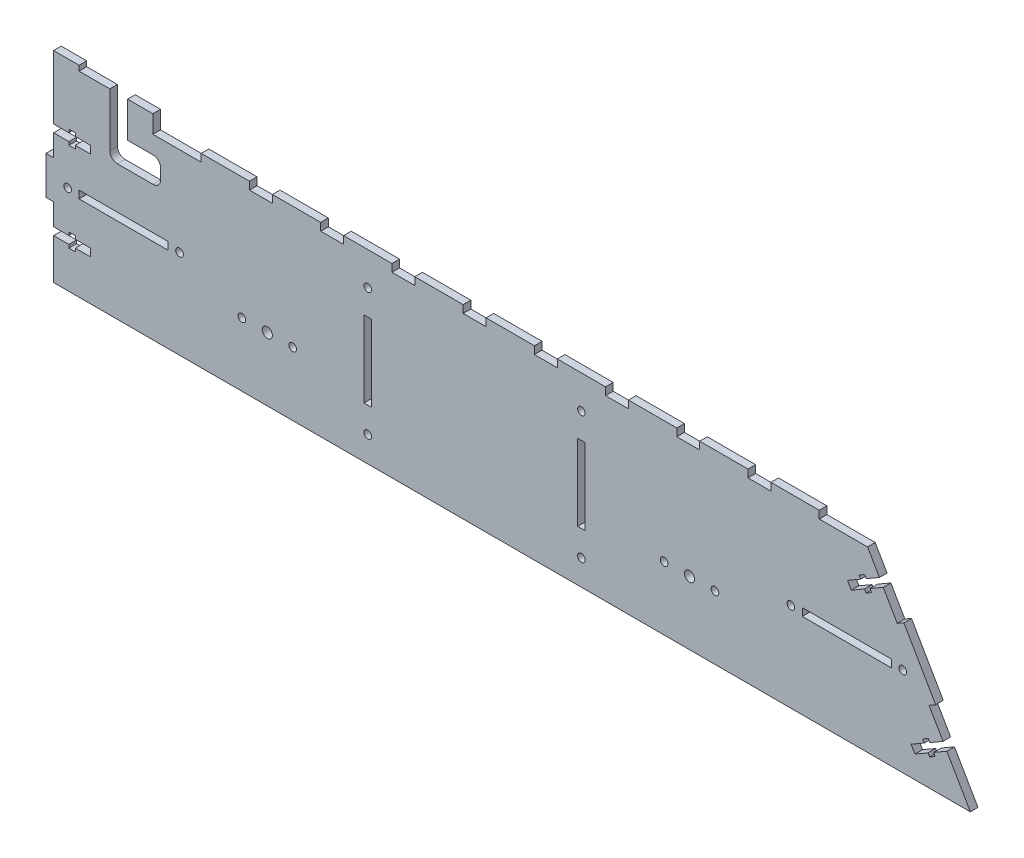
SolidWorks part; units mm, degrees
ref_plane "Спереди" through (0, 0, 0) normal (0, 0, 1) x (1, 0, 0)
ref_plane "Сверху" through (0, 0, 0) normal (0, 1, 0) x (1, 0, 0)
ref_plane "Справа" through (0, 0, 0) normal (1, 0, 0) x (0, 0, -1)
sketch "Эскиз1" plane through (0, 0, 0) normal (0, 0, 1) x (1, 0, 0)
  line L0 (320, 70) -> (360.4145, 0)
  line L2 (0, 0) -> (0, 70)
  line L3 (0, 70) -> (320, 70)
  line L5 (0, 0) -> (360.4145, 0)
  circle A0 centre (84, 25) radius 2
  circle A1 centre (250, 25) radius 2
  circle A2 centre (84, 25) radius 10 construction
  circle A3 centre (94, 25) radius 1.5
  circle A4 centre (74, 25) radius 1.5
  circle A5 centre (240, 25) radius 1.5
  circle A6 centre (260, 25) radius 1.5
  circle A7 centre (250, 25) radius 10 construction
  dimension "D4" = 4
  dimension "D8" = 20
  dimension "D9" = 3
  dimension "D10" = 80.829
  dimension "D1" = 320
  dimension "D2" = 70
  dimension "D3" = 60
  dimension "D5" = 25
  dimension "D6" = 166
  dimension "D7" = 84
extrude "Бобышка-Вытянуть1" add sketch "Эскиз1" along normal blind 3
sketch "Эскиз2" plane through (0, 70, 0) normal (0, 1, 0) x (1, 0, 0)
  line L0 (320, -3) -> (0, -3) construction
  line L1 (301, -3) -> (282, -3)
  line L2 (301, -3) -> (301, 0)
  line L3 (301, 0) -> (282, 0)
  line L4 (282, -3) -> (282, 0)
  line L5 (320, 0) -> (0, 0) construction
  dimension "D1" = 19
  dimension "D2" = 19
extrude "Бобышка-Вытянуть2" add sketch "Эскиз2" along normal blind 3
pattern_linear "Линейный массив1" count 9 spacing 28 along (-1, 0, 0) of "Бобышка-Вытянуть2"
sketch "Эскиз3" plane through (0, 0, 3) normal (0, 0, 1) x (1, 0, 0)
  line L0 (198, 73) -> (217, 73) construction
  line L1 (206, 50) -> (209, 50)
  line L2 (206, 50) -> (206, 20)
  line L3 (206, 20) -> (209, 20)
  line L4 (209, 50) -> (209, 20)
  line L5 (206, 50) -> (209, 20) construction
  line L6 (206, 20) -> (209, 50) construction
  line L7 (0, 70) -> (0, 0) construction
  line L8 (114, 73) -> (133, 73) construction
  line L9 (122, 50) -> (125, 50)
  line L10 (122, 50) -> (122, 20)
  line L11 (122, 20) -> (125, 20)
  line L12 (125, 50) -> (125, 20)
  line L13 (122, 50) -> (125, 20) construction
  line L14 (122, 20) -> (125, 50) construction
  point P0 (207.5, 35)
  point P9 (207.5, 73)
  point P10 (123.5, 73)
  point P13 (0, 35)
  point P14 (123.5, 35)
  point P19 (123.5, 20)
  point P21 (207.5, 20)
  dimension "D3" = 123.5
  dimension "D1" = 30
  dimension "D2" = 3
  dimension "D4" = 84
extrude "Вырез-Вытянуть1" cut sketch "Эскиз3" against normal blind 3
sketch "Эскиз4" plane through (0, 0, 3) normal (0, 0, 1) x (1, 0, 0)
  line L0 (0, 70) -> (0, 0) construction
  line L1 (294.3412, 36.5) -> (329.3412, 36.5)
  line L2 (294.3412, 36.5) -> (294.3412, 33.5)
  line L3 (294.3412, 33.5) -> (329.3412, 33.5)
  line L4 (329.3412, 36.5) -> (329.3412, 33.5)
  line L5 (294.3412, 36.5) -> (329.3412, 33.5) construction
  line L6 (294.3412, 33.5) -> (329.3412, 36.5) construction
  line L7 (10, 36.5) -> (45, 36.5)
  line L8 (10, 36.5) -> (10, 33.5)
  line L9 (10, 33.5) -> (45, 33.5)
  line L10 (45, 36.5) -> (45, 33.5)
  line L11 (10, 36.5) -> (45, 33.5) construction
  line L12 (10, 33.5) -> (45, 36.5) construction
  line L14 (329.3412, 36.5) -> (339.3412, 36.5) construction
  line L15 (360.4145, 0) -> (320, 70) construction
  circle A0 centre (84, 25) radius 35 construction
  point P0 (311.8412, 35)
  point P5 (27.5, 35)
  point P15 (0, 35)
  point P18 (340.2073, 35)
  dimension "D5" = 70
  dimension "D1" = 35
  dimension "D2" = 3
  dimension "D3" = 10
  dimension "D4" = 10
  dimension "D6" = 40.4145
  dimension "D7" = 284.3412
extrude "Вырез-Вытянуть2" cut sketch "Эскиз4" against normal blind 3
sketch "Эскиз5" plane through (0, 0, 3) normal (0, 0, 1) x (1, 0, 0)
  line L0 (125, 50) -> (122, 50) construction
  line L1 (209, 50) -> (206, 50) construction
  line L2 (294.3412, 36.5) -> (294.3412, 33.5) construction
  line L3 (10, 36.5) -> (10, 33.5) construction
  circle A0 centre (5.5, 35) radius 1.5
  circle A1 centre (49.5, 35) radius 1.5
  circle A2 centre (123.5, 60) radius 1.5
  circle A3 centre (123.5, 10) radius 1.5
  circle A4 centre (207.5, 60) radius 1.5
  circle A5 centre (207.5, 10) radius 1.5
  circle A6 centre (289.8412, 35) radius 1.5
  circle A7 centre (333.8412, 35) radius 1.5
  point P20 (123.5, 50)
  point P29 (207.5, 50)
  point P34 (294.3412, 35)
  point P42 (10, 35)
  dimension "D1" = 3
  dimension "D2" = 10
  dimension "D3" = 10
  dimension "D4" = 4.5
  dimension "D5" = 4.5
  dimension "D6" = 4.5
  dimension "D7" = 4.5
extrude "Вырез-Вытянуть3" cut sketch "Эскиз5" against normal blind 3
sketch "Эскиз6" plane through (0, 0, 3) normal (0, 0, 1) x (1, 0, 0)
  line L0 (0, 54) -> (6, 54)
  line L1 (6, 54) -> (6, 55.25)
  line L2 (6, 55.25) -> (8.5, 55.25)
  line L3 (8.5, 55.25) -> (8.5, 54)
  line L4 (8.5, 54) -> (14.5, 54)
  line L5 (14.5, 54) -> (14.5, 51)
  line L6 (14.5, 51) -> (8.5, 51)
  line L7 (8.5, 51) -> (8.5, 49.75)
  line L8 (8.5, 49.75) -> (6, 49.75)
  line L9 (6, 49.75) -> (6, 51)
  line L10 (6, 51) -> (0, 51)
  line L13 (0, 19) -> (6, 19)
  line L14 (6, 19) -> (6, 20.25)
  line L15 (6, 20.25) -> (8.5, 20.25)
  line L16 (8.5, 20.25) -> (8.5, 19)
  line L17 (8.5, 19) -> (14.5, 19)
  line L18 (14.5, 19) -> (14.5, 16)
  line L19 (14.5, 16) -> (8.5, 16)
  line L20 (8.5, 16) -> (8.5, 14.75)
  line L21 (8.5, 14.75) -> (6, 14.75)
  line L22 (6, 14.75) -> (6, 16)
  line L23 (6, 16) -> (0, 16)
  line L24 (0, 70) -> (0, 0) construction
  line L25 (0, 0) -> (360.4145, 0) construction
  line L26 (0, 54) -> (0, 51)
  line L27 (0, 19) -> (0, 16)
  point P12 (7.25, 49.75)
  point P28 (7.25, 14.75)
  point P31 (14.5, 52.5)
  point P32 (14.5, 17.5)
  dimension "D1" = 2.5
  dimension "D2" = 3
  dimension "D3" = 5.5
  dimension "D4" = 6
  dimension "D5" = 6
  dimension "D6" = 2.5
  dimension "D7" = 3
  dimension "D8" = 5.5
  dimension "D9" = 6
  dimension "D10" = 6
  dimension "D11" = 35
  dimension "D12" = 17.5
extrude "Вырез-Вытянуть4" cut sketch "Эскиз6" against normal blind 3
sketch "Эскиз7" plane through (0, 0, 3) normal (0, 0, 1) x (1, 0, 0)
  line L0 (324.6645, 61.9208) -> (319.4684, 58.9208)
  line L1 (319.4684, 58.9208) -> (318.8434, 60.0033)
  line L2 (318.8434, 60.0033) -> (316.6783, 58.7533)
  line L3 (316.6783, 58.7533) -> (317.3033, 57.6708)
  line L4 (317.3033, 57.6708) -> (312.1072, 54.6708)
  line L5 (312.1072, 54.6708) -> (313.6072, 52.0727)
  line L6 (313.6072, 52.0727) -> (318.8033, 55.0727)
  line L7 (318.8033, 55.0727) -> (319.4283, 53.9902)
  line L8 (319.4283, 53.9902) -> (321.5934, 55.2402)
  line L9 (321.5934, 55.2402) -> (320.9684, 56.3227)
  line L10 (320.9684, 56.3227) -> (326.1645, 59.3227)
  line L11 (326.1645, 59.3227) -> (324.6645, 61.9208)
  line L12 (349.6645, 18.6195) -> (344.4684, 15.6195)
  line L13 (344.4684, 15.6195) -> (343.8434, 16.7021)
  line L14 (343.8434, 16.7021) -> (341.6783, 15.4521)
  line L15 (341.6783, 15.4521) -> (342.3033, 14.3695)
  line L16 (342.3033, 14.3695) -> (337.1072, 11.3695)
  line L17 (337.1072, 11.3695) -> (338.6072, 8.7715)
  line L18 (338.6072, 8.7715) -> (343.8033, 11.7715)
  line L19 (343.8033, 11.7715) -> (344.4283, 10.6889)
  line L20 (344.4283, 10.6889) -> (346.5934, 11.9389)
  line L21 (346.5934, 11.9389) -> (345.9684, 13.0215)
  line L22 (345.9684, 13.0215) -> (351.1645, 16.0215)
  line L23 (351.1645, 16.0215) -> (349.6645, 18.6195)
  line L24 (360.4145, 0) -> (320, 70) construction
  point P24 (350.4145, 17.3205)
  dimension "D1" = 6
  dimension "D2" = 2.5
  dimension "D3" = 3
  dimension "D4" = 5.5
  dimension "D5" = 6
  dimension "D6" = 2.5
  dimension "D7" = 3
  dimension "D8" = 5.5
  dimension "D9" = 50
  dimension "D10" = 20
extrude "Вырез-Вытянуть5" cut sketch "Эскиз7" against normal blind 3
sketch "Эскиз8" plane through (0, 70, 0) normal (0, 1, 0) x (1, 0, 0)
  line L0 (58, -3) -> (0, -3) construction
  line L1 (0, 0) -> (39, 0)
  line L2 (0, 0) -> (0, -3)
  line L3 (0, -3) -> (39, -3)
  line L4 (39, 0) -> (39, -3)
  dimension "D1" = 39
extrude "Бобышка-Вытянуть3" add sketch "Эскиз8" along normal blind 9
sketch "Эскиз9" plane through (0, 79, 0) normal (0, 1, 0) x (1, 0, 0)
  line L0 (0, -3) -> (39, -3) construction
  line L1 (39, 0) -> (10, 0)
  line L2 (39, 0) -> (39, -3)
  line L3 (39, -3) -> (10, -3)
  line L4 (10, 0) -> (10, -3)
  dimension "D1" = 10
extrude "Вырез-Вытянуть6" cut sketch "Эскиз9" against normal blind 2
sketch "Эскиз11" plane through (270.3109, 156.0641, 0) normal (0.866, 0.5, 0) x (0, 0, -1)
  line L0 (-3, -158.7073) -> (-3, -111.7073) construction
  line L1 (-3, -147.7073) -> (0, -147.7073)
  line L2 (-3, -147.7073) -> (-3, -122.7073)
  line L3 (-3, -122.7073) -> (0, -122.7073)
  line L4 (0, -147.7073) -> (0, -122.7073)
  line L5 (0, -158.7073) -> (0, -111.7073) construction
  point P9 (-3, -135.2073)
  point P10 (-3, -135.2073)
  dimension "D1" = 25
extrude "Бобышка-Вытянуть5" add sketch "Эскиз11" along normal blind 3
sketch "Эскиз12" plane through (0, 0, 0) normal (-1, 0, 0) x (0, 0, 1)
  line L0 (0, 51) -> (0, 19) construction
  line L1 (0, 27.5) -> (3, 27.5)
  line L2 (0, 27.5) -> (0, 42.5)
  line L3 (0, 42.5) -> (3, 42.5)
  line L4 (3, 27.5) -> (3, 42.5)
  line L5 (3, 51) -> (3, 19) construction
  point P9 (0, 35)
  point P10 (0, 35)
  dimension "D1" = 15
extrude "Бобышка-Вытянуть6" add sketch "Эскиз12" along normal blind 3
sketch "Эскиз13" plane through (0, 0, 3) normal (0, 0, 1) x (1, 0, 0)
  line L0 (22.0756, 62.9952) -> (22.0756, 77)
  line L1 (22.0756, 52.9952) -> (42.0756, 52.9952)
  line L2 (22.0756, 52.9952) -> (22.0756, 62.9952)
  line L3 (29.0756, 62.9952) -> (42.0756, 62.9952)
  line L4 (42.0756, 52.9952) -> (42.0756, 62.9952)
  line L5 (10, 77) -> (39, 77) construction
  line L6 (22.0756, 77) -> (29.0756, 77)
  line L7 (29.0756, 77) -> (29.0756, 62.9952)
  dimension "D1" = 10
  dimension "D2" = 20
  dimension "D3" = 7
extrude "Вырез-Вытянуть7" cut sketch "Эскиз13" against normal blind 3
fillet "Скругление1" radius 3 3 edges at (22.0756, 52.9952, 1.5) (42.0756, 62.9952, 1.5) (42.0756, 52.9952, 1.5)
